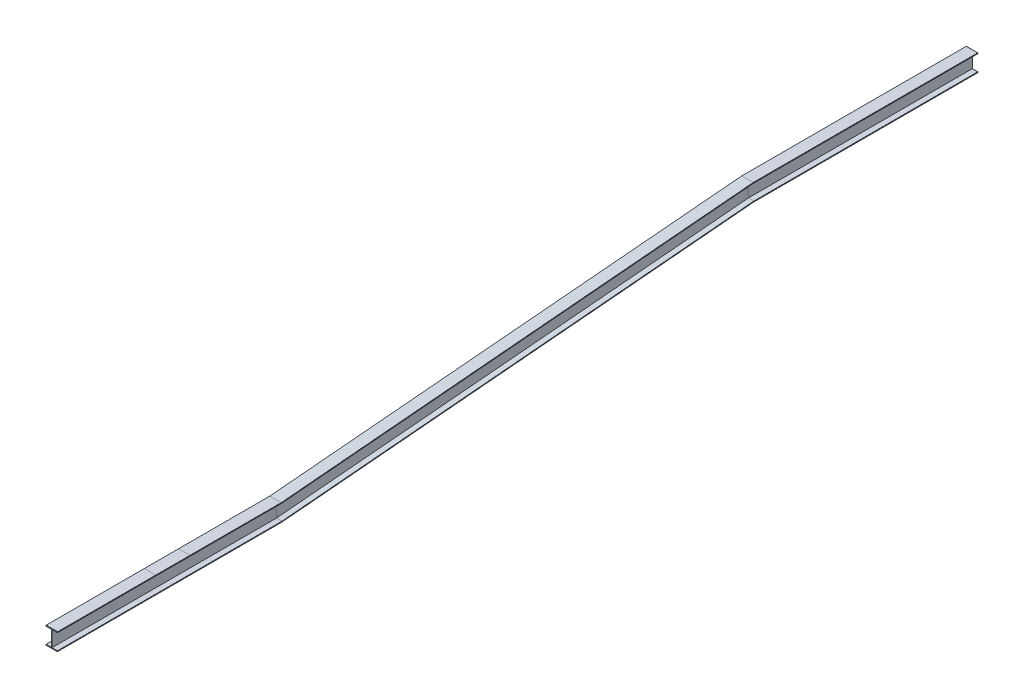
SolidWorks part; units mm, degrees
material "ASTM A992 Steel"
ref_plane "Front" through (0, 0, 0) normal (0, 0, 1) x (1, 0, 0)
ref_plane "Top" through (0, 0, 0) normal (0, 1, 0) x (1, 0, 0)
ref_plane "Right" through (0, 0, 0) normal (1, 0, 0) x (0, 0, -1)
sketch "Sketch1" plane through (0, 0, 0) normal (0, 0, 1) x (1, 0, 0)
  line L0 (0, -0.0002) -> (101.6, -0.0002)
  line L1 (101.6, -0.0002) -> (101.6, -7.1122)
  line L2 (101.6, -7.1122) -> (53.408, -7.1122)
  line L3 (53.408, -7.1122) -> (53.408, -146.0502)
  line L4 (53.408, -146.0502) -> (101.6, -146.0502)
  line L5 (101.6, -146.0502) -> (101.6, -153.1622)
  line L6 (101.6, -153.1622) -> (0, -153.1622)
  line L7 (0, -153.1622) -> (0, -146.0502)
  line L8 (0, -146.0502) -> (47.566, -146.0502)
  line L9 (47.566, -146.0502) -> (47.566, -7.1122)
  line L10 (47.566, -7.1122) -> (0, -7.1122)
  line L11 (0, -7.1122) -> (0, -0.0002)
  line L12 (50.8, -0.0002) -> (50.8, -153.1622) construction
  point P15 (50.8, -76.5812)
  dimension "D1" = 5.842
  dimension "D2" = 7.112
  dimension "D3" = 7.112
  dimension "D4" = 7.112
  dimension "D5" = 153.162
  dimension "D6" = 50.8
  dimension "D7" = 50.8
  dimension "D8" = 47.566
sketch "Sketch2" plane through (0, 0, 0) normal (1, 0, 0) x (0, 0, -1)
  line L0 (0, -76.5812) -> (1930, -76.5812)
  line L1 (1930, -76.5812) -> (6128.7777, 290.7642)
  line L2 (6128.7777, 290.7642) -> (8058.7777, 290.7642)
  line L3 (1930, -76.5812) -> (909.297, -76.5812) construction
  dimension "D1" = 5
  dimension "D2" = 1930
  dimension "D3" = 4214.8163
  dimension "D4" = 1930
sweep "Sweep1" add profiles "Sketch1" path "Sketch2"
sketch "Sketch3" plane through (0, -0.0002, 0) normal (0, 1, 0) x (1, 0, 0)
  line L0 (101.6, 0) -> (101.6, 1926.6564) construction
  line L1 (101.6, 963.3282) -> (101.6, 810.9282)
  line L2 (101.6, 810.9282) -> (0, 810.9282)
  line L3 (0, 0) -> (0, 1926.6564) construction
  line L4 (0, 810.9282) -> (0, 963.3282)
  line L5 (0, 963.3282) -> (0, 1115.7282)
  line L6 (0, 1115.7282) -> (101.6, 1115.7282)
  line L7 (101.6, 1115.7282) -> (101.6, 963.3282)
  point P0 (101.6, 963.3282)
  dimension "D1" = 152.4
  dimension "D2" = 152.4
split line "Split Line1"
sketch "Sketch4" plane through (0, 0, -8058.7777) normal (0, 0, -1) x (-1, 0, 0)
  line L12 (0, 360.2332) -> (0, 367.3452)
  line L13 (0, 367.3452) -> (-101.6, 367.3452)
  line L14 (-101.6, 367.3452) -> (-101.6, 360.2332)
  line L15 (-101.6, 360.2332) -> (-53.408, 360.2332)
  line L16 (-53.408, 360.2332) -> (-53.408, 221.2952)
  line L17 (-53.408, 221.2952) -> (-101.6, 221.2952)
  line L18 (-101.6, 221.2952) -> (-101.6, 214.1832)
  line L19 (-101.6, 214.1832) -> (0, 214.1832)
  line L20 (0, 214.1832) -> (0, 221.2952)
  line L21 (0, 221.2952) -> (-47.566, 221.2952)
  line L22 (-47.566, 221.2952) -> (-47.566, 360.2332)
  line L23 (-47.566, 360.2332) -> (0, 360.2332)
  line L24 (0, 360.2332) -> (0, 367.3452)
  line L25 (0, 367.3452) -> (-101.6, 367.3452)
  line L26 (-101.6, 367.3452) -> (-101.6, 360.2332)
  line L27 (-101.6, 360.2332) -> (-53.408, 360.2332)
  line L28 (-53.408, 360.2332) -> (-53.408, 221.2952)
  line L29 (-53.408, 221.2952) -> (-101.6, 221.2952)
  line L30 (-101.6, 221.2952) -> (-101.6, 214.1832)
  line L31 (-101.6, 214.1832) -> (0, 214.1832)
  line L32 (0, 214.1832) -> (0, 221.2952)
  line L33 (0, 221.2952) -> (-47.566, 221.2952)
  line L34 (-47.566, 221.2952) -> (-47.566, 360.2332)
  line L35 (-47.566, 360.2332) -> (0, 360.2332)
  dimension "D1" = 0
extrude "Boss-Extrude1" add sketch "Sketch4" along normal up to surface (14.5416 mm away)
sketch "Sketch5" plane through (0, 0, 0) normal (0, 0, 1) x (1, 0, 0)
  line L12 (0, -0.0002) -> (0, -7.1122)
  line L13 (0, -7.1122) -> (47.566, -7.1122)
  line L14 (47.566, -7.1122) -> (47.566, -146.0502)
  line L15 (47.566, -146.0502) -> (0, -146.0502)
  line L16 (0, -146.0502) -> (0, -153.1622)
  line L17 (0, -153.1622) -> (101.6, -153.1622)
  line L18 (101.6, -153.1622) -> (101.6, -146.0502)
  line L19 (101.6, -146.0502) -> (53.408, -146.0502)
  line L20 (53.408, -146.0502) -> (53.408, -7.1122)
  line L21 (53.408, -7.1122) -> (101.6, -7.1122)
  line L22 (101.6, -7.1122) -> (101.6, -0.0002)
  line L23 (101.6, -0.0002) -> (0, -0.0002)
  line L24 (0, -0.0002) -> (0, -7.1122)
  line L25 (0, -7.1122) -> (47.566, -7.1122)
  line L26 (47.566, -7.1122) -> (47.566, -146.0502)
  line L27 (47.566, -146.0502) -> (0, -146.0502)
  line L28 (0, -146.0502) -> (0, -153.1622)
  line L29 (0, -153.1622) -> (101.6, -153.1622)
  line L30 (101.6, -153.1622) -> (101.6, -146.0502)
  line L31 (101.6, -146.0502) -> (53.408, -146.0502)
  line L32 (53.408, -146.0502) -> (53.408, -7.1122)
  line L33 (53.408, -7.1122) -> (101.6, -7.1122)
  line L34 (101.6, -7.1122) -> (101.6, -0.0002)
  line L35 (101.6, -0.0002) -> (0, -0.0002)
  dimension "D1" = 0
extrude "Boss-Extrude2" add sketch "Sketch5" along normal up to surface (11.1092 mm away)
sketch "Sketch6" plane through (0, 0, -8073.3193) normal (0, 0, -1) x (-1, 0, 0)
  line L12 (-47.566, 221.2952) -> (-47.566, 360.2332)
  line L13 (-47.566, 360.2332) -> (0, 360.2332)
  line L14 (0, 360.2332) -> (0, 367.3452)
  line L15 (0, 367.3452) -> (-101.6, 367.3452)
  line L16 (-101.6, 367.3452) -> (-101.6, 360.2332)
  line L17 (-101.6, 360.2332) -> (-53.408, 360.2332)
  line L18 (-53.408, 360.2332) -> (-53.408, 221.2952)
  line L19 (-53.408, 221.2952) -> (-101.6, 221.2952)
  line L20 (-101.6, 221.2952) -> (-101.6, 214.1832)
  line L21 (-101.6, 214.1832) -> (0, 214.1832)
  line L22 (0, 214.1832) -> (0, 221.2952)
  line L23 (0, 221.2952) -> (-47.566, 221.2952)
  line L24 (-47.566, 221.2952) -> (-47.566, 360.2332)
  line L25 (-47.566, 360.2332) -> (0, 360.2332)
  line L26 (0, 360.2332) -> (0, 367.3452)
  line L27 (0, 367.3452) -> (-101.6, 367.3452)
  line L28 (-101.6, 367.3452) -> (-101.6, 360.2332)
  line L29 (-101.6, 360.2332) -> (-53.408, 360.2332)
  line L30 (-53.408, 360.2332) -> (-53.408, 221.2952)
  line L31 (-53.408, 221.2952) -> (-101.6, 221.2952)
  line L32 (-101.6, 221.2952) -> (-101.6, 214.1832)
  line L33 (-101.6, 214.1832) -> (0, 214.1832)
  line L34 (0, 214.1832) -> (0, 221.2952)
  line L35 (0, 221.2952) -> (-47.566, 221.2952)
  dimension "D1" = 0
extrude "Boss-Extrude4" [suppressed] add sketch "Sketch6" along normal up to surface (73.152 mm away)
fillet "Fillet1" [suppressed] radius 22.7686
sketch "Sketch7" plane through (0, 0, 11.1092) normal (0, 0, 1) x (1, 0, 0)
  line L12 (101.6, -7.1122) -> (101.6, -0.0002)
  line L13 (101.6, -0.0002) -> (0, -0.0002)
  line L14 (0, -0.0002) -> (0, -7.1122)
  line L15 (0, -7.1122) -> (47.566, -7.1122)
  line L16 (47.566, -7.1122) -> (47.566, -146.0502)
  line L17 (47.566, -146.0502) -> (0, -146.0502)
  line L18 (0, -146.0502) -> (0, -153.1622)
  line L19 (0, -153.1622) -> (101.6, -153.1622)
  line L20 (101.6, -153.1622) -> (101.6, -146.0502)
  line L21 (101.6, -146.0502) -> (53.408, -146.0502)
  line L22 (53.408, -146.0502) -> (53.408, -7.1122)
  line L23 (53.408, -7.1122) -> (101.6, -7.1122)
  line L24 (101.6, -7.1122) -> (101.6, -0.0002)
  line L25 (101.6, -0.0002) -> (0, -0.0002)
  line L26 (0, -0.0002) -> (0, -7.1122)
  line L27 (0, -7.1122) -> (47.566, -7.1122)
  line L28 (47.566, -7.1122) -> (47.566, -146.0502)
  line L29 (47.566, -146.0502) -> (0, -146.0502)
  line L30 (0, -146.0502) -> (0, -153.1622)
  line L31 (0, -153.1622) -> (101.6, -153.1622)
  line L32 (101.6, -153.1622) -> (101.6, -146.0502)
  line L33 (101.6, -146.0502) -> (53.408, -146.0502)
  line L34 (53.408, -146.0502) -> (53.408, -7.1122)
  line L35 (53.408, -7.1122) -> (101.6, -7.1122)
  dimension "D1" = 0
extrude "Boss-Extrude5" add sketch "Sketch7" along normal up to surface (52.832 mm away)
sketch "Sketch8" plane through (0, 0, -8073.3193) normal (0, 0, -1) x (-1, 0, 0)
  line L12 (-47.566, 221.2952) -> (-47.566, 360.2332)
  line L13 (-47.566, 360.2332) -> (0, 360.2332)
  line L14 (0, 360.2332) -> (0, 367.3452)
  line L15 (0, 367.3452) -> (-101.6, 367.3452)
  line L16 (-101.6, 367.3452) -> (-101.6, 360.2332)
  line L17 (-101.6, 360.2332) -> (-53.408, 360.2332)
  line L18 (-53.408, 360.2332) -> (-53.408, 221.2952)
  line L19 (-53.408, 221.2952) -> (-101.6, 221.2952)
  line L20 (-101.6, 221.2952) -> (-101.6, 214.1832)
  line L21 (-101.6, 214.1832) -> (0, 214.1832)
  line L22 (0, 214.1832) -> (0, 221.2952)
  line L23 (0, 221.2952) -> (-47.566, 221.2952)
  line L24 (-47.566, 221.2952) -> (-47.566, 360.2332)
  line L25 (-47.566, 360.2332) -> (0, 360.2332)
  line L26 (0, 360.2332) -> (0, 367.3452)
  line L27 (0, 367.3452) -> (-101.6, 367.3452)
  line L28 (-101.6, 367.3452) -> (-101.6, 360.2332)
  line L29 (-101.6, 360.2332) -> (-53.408, 360.2332)
  line L30 (-53.408, 360.2332) -> (-53.408, 221.2952)
  line L31 (-53.408, 221.2952) -> (-101.6, 221.2952)
  line L32 (-101.6, 221.2952) -> (-101.6, 214.1832)
  line L33 (-101.6, 214.1832) -> (0, 214.1832)
  line L34 (0, 214.1832) -> (0, 221.2952)
  line L35 (0, 221.2952) -> (-47.566, 221.2952)
  dimension "D1" = 0
extrude "Boss-Extrude6" add sketch "Sketch8" along normal up to surface (52.832 mm away)
fillet "Fillet2" radius 3.175 2 edges at (50.8, -0.0002, 63.9412) (50.8, 367.3452, -8126.1513)
sketch "Sketch9" plane through (0, 214.1832, 0) normal (0, -1, 0) x (1, 0, 0)
  line L4 (101.6, -6132.1213) -> (0, -6132.1213)
  line L5 (0, -6132.1213) -> (0, -8126.1513)
  line L6 (0, -8126.1513) -> (101.6, -8126.1513)
  line L7 (101.6, -8126.1513) -> (101.6, -6132.1213)
  line L8 (101.6, -6132.1213) -> (0, -6132.1213)
  line L9 (0, -6132.1213) -> (0, -8126.1513)
  line L10 (0, -8126.1513) -> (101.6, -8126.1513)
  line L11 (101.6, -8126.1513) -> (101.6, -6132.1213)
  dimension "D1" = 0
extrude "Boss-Extrude7" add sketch "Sketch9" along normal up to surface (0.194 mm away)
fillet "Fillet3" radius 3.175 2 edges at (77.504, 221.2952, -8126.1513) (23.783, 221.2952, -8126.1513)
